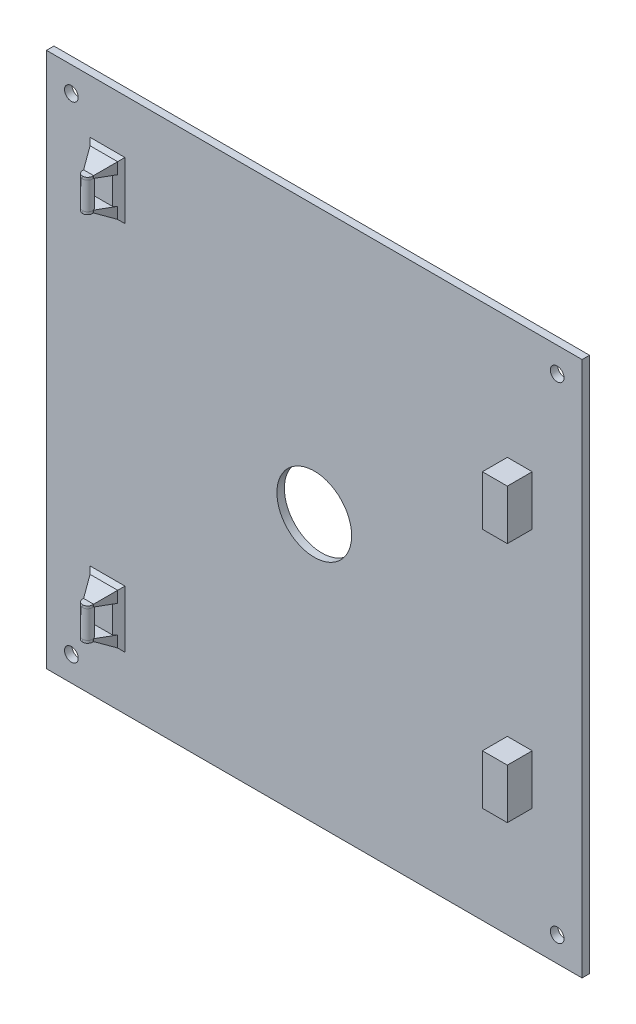
SolidWorks part; units mm, degrees
material "6061 합금"
ref_plane "정면" through (0, 0, 0) normal (0, 0, 1) x (1, 0, 0)
ref_plane "윗면" through (0, 0, 0) normal (0, 1, 0) x (1, 0, 0)
ref_plane "우측면" through (0, 0, 0) normal (1, 0, 0) x (0, 0, -1)
sketch "스케치1" plane through (0, 0, 0) normal (0, 0, 1) x (1, 0, 0)
  line L1 (-107.5, 107.5) -> (107.5, 107.5)
  line L2 (-107.5, 107.5) -> (-107.5, -107.5)
  line L3 (-107.5, -107.5) -> (107.5, -107.5)
  line L4 (107.5, 107.5) -> (107.5, -107.5)
  line L5 (-107.5, 107.5) -> (107.5, -107.5) construction
  line L6 (-107.5, -107.5) -> (107.5, 107.5) construction
  point P0 (0, 0)
  dimension "D1" = 215
  dimension "D2" = 215
extrude "보스-돌출1" add sketch "스케치1" along normal blind 3 contours L1 L4 L3 L2
hole_wizard "M5 여유 구멍1" positions "스케치2" profile "스케치3" hole size "M5" standard "KS" end condition through all
sketch "스케치2" plane through (0, 0, 3) normal (0, 0, 1) x (1, 0, 0)
  line L0 (-107.5, -107.5) -> (107.5, -107.5) construction
  line L1 (-107.5, 107.5) -> (-107.5, -107.5) construction
  line L3 (-107.5, 107.5) -> (107.5, 107.5) construction
  line L4 (107.5, 107.5) -> (107.5, -107.5) construction
  point P0 (-97.5, -97.5)
  point P2 (-97.5, 97.5)
  point P4 (97.5, 97.5)
  point P6 (97.5, -97.5)
  dimension "D1" = 10
  dimension "D2" = 10
  dimension "D3" = 10
  dimension "D4" = 10
  dimension "D5" = 10
  dimension "D6" = 10
  dimension "D7" = 10
  dimension "D8" = 10
sketch "스케치3" plane through (-97.5, -97.5, 3) normal (1, 0, 0) x (0, -1, 0)
  line L0 (0, 0) -> (0, 3)
  line L1 (0, 3) -> (2.75, 3)
  line L2 (2.75, 3) -> (2.75, 0)
  line L5 (2.75, 0) -> (0, 0)
  line L11 (0, -6.35) -> (0, 107.95) construction
  dimension "관통 구멍 지름" = 5.5
  dimension "관통 구멍 깊이" = 3
sketch "스케치4" plane through (0, 0, 3) normal (0, 0, 1) x (1, 0, 0)
  circle A0 centre (0, 0) radius 15
  dimension "D1" = 30
extrude "컷-돌출1" cut sketch "스케치4" against normal blind 10
sketch "스케치6" plane through (0, 0, 0) normal (0, 0, 1) x (1, 0, 0)
  line L1 (-125, 125) -> (125, 125) construction
  line L2 (-125, 125) -> (-125, -125) construction
  line L3 (-125, -125) -> (125, -125) construction
  line L4 (125, 125) -> (125, -125) construction
  line L5 (-125, 125) -> (125, -125) construction
  line L6 (-125, -125) -> (125, 125) construction
  point P0 (0, 0)
  dimension "D1" = 250
  dimension "D2" = 250
sketch "스케치5" plane through (0, 0, 3) normal (0, 0, 1) x (1, 0, 0)
  line L0 (-107.5, 107.5) -> (107.5, 107.5) construction
  line L1 (-85, 81) -> (-81, 81)
  line L2 (-85, 81) -> (-85, 68)
  line L3 (-85, 68) -> (-81, 68)
  line L4 (-81, 81) -> (-81, 68)
  line L5 (-85, -68) -> (-81, -68)
  line L6 (-85, -68) -> (-85, -81)
  line L7 (-85, -81) -> (-81, -81)
  line L8 (-81, -68) -> (-81, -81)
  line L9 (77.5, -38.5) -> (87.5, -38.5)
  line L10 (77.5, -38.5) -> (77.5, -58.5)
  line L11 (77.5, -58.5) -> (87.5, -58.5)
  line L12 (87.5, -38.5) -> (87.5, -58.5)
  line L13 (77.5, 58.5) -> (87.5, 58.5)
  line L14 (77.5, 58.5) -> (77.5, 38.5)
  line L15 (77.5, 38.5) -> (87.5, 38.5)
  line L16 (87.5, 58.5) -> (87.5, 38.5)
  line L18 (-107.5, -107.5) -> (107.5, -107.5) construction
  line L19 (107.5, 107.5) -> (107.5, -107.5) construction
  line L20 (-125, 125) -> (125, 125) construction
  line L21 (-125, -125) -> (125, -125) construction
  line L22 (-125, 125) -> (-125, -125) construction
  dimension "D1" = 13
  dimension "D2" = 13
  dimension "D3" = 4
  dimension "D4" = 4
  dimension "D5" = 10
  dimension "D6" = 20
  dimension "D7" = 20
  dimension "D8" = 10
  dimension "D9" = 44
  dimension "D10" = 40
  dimension "D11" = 40
  dimension "D12" = 44
  dimension "D13" = 49
  dimension "D14" = 20
  dimension "D15" = 20
  dimension "D16" = 49
extrude "보스-돌출2" add sketch "스케치5" along normal blind 10
chamfer "모따기1" distance 5 angle 45 4 edges at (-83, 68, 3) (-83, 81, 3) (-83, -68, 3) (-83, -81, 3)
sketch "스케치7" plane through (-85, 0, 0) normal (-1, 0, 0) x (0, 0, 1)
  line L0 (13, -68) -> (8, -68) construction
  line L1 (5.5, -69) -> (13, -69)
  line L2 (5.5, -69) -> (5.5, -80)
  line L3 (5.5, -80) -> (13, -80)
  line L4 (13, -69) -> (13, -80)
  line L5 (13, -81) -> (8, -81) construction
  line L6 (13, -68) -> (13, -81) construction
  dimension "D1" = 1
  dimension "D2" = 1
  dimension "D3" = 0
  dimension "D4" = 7.5
extrude "컷-돌출2" cut sketch "스케치7" against normal blind 10
mirror "대칭 복사3" about plane through (0, 0, 0) normal (0, 1, 0) of "컷-돌출2"
sketch "스케치8" plane through (0, -69, 0) normal (0, -1, 0) x (1, 0, 0)
  line L1 (-85, 13) -> (-85, 5.5) construction
  line L2 (-81, 13) -> (-85, 13) construction
  circle A0 centre (-83, 11) radius 2
  dimension "D2" = 4
  dimension "D1" = 2
  dimension "D3" = 2
extrude "보스-돌출3" add sketch "스케치8" along normal up to next
mirror "대칭 복사4" about plane through (0, 0, 0) normal (0, 1, 0) of "보스-돌출3"
fillet "필렛1" radius 2 8 edges at (-85, -80.5, 13) (-81, -80.5, 13) (-81, -68.5, 13) (-85, -68.5, 13) (-81, 68.5, 13) (-81, 80.5, 13) (-85, 80.5, 13) (-85, 68.5, 13)
chamfer "모따기2" distance 5 angle 45 4 edges at (-81, -74.5, 3) (-85, -74.5, 3) (-81, 74.5, 3) (-85, 74.5, 3)
chamfer "모따기3" distance 5 angle 15 12 edges at (-85, -68.5, 8) (-81, -80.5, 8) (-83, -81, 8) (-85, -80.5, 8) (-81, -68.5, 8) (-83, -68, 8) (-85, 68.5, 8) (-83, 68, 8) (-81, 68.5, 8) (-81, 80.5, 8) (-83, 81, 8) (-85, 80.5, 8) first distance on face at (-86.875, -74.5, 6.125) first distance on face at (-79.125, -74.5, 6.125) first distance on face at (-83, -83.5, 5.5) first distance on face at (-83, -65.5, 5.5) first distance on face at (-86.875, 74.5, 6.125) first distance on face at (-83, 65.5, 5.5) first distance on face at (-79.125, 74.5, 6.125) first distance on face at (-83, 83.5, 5.5)
